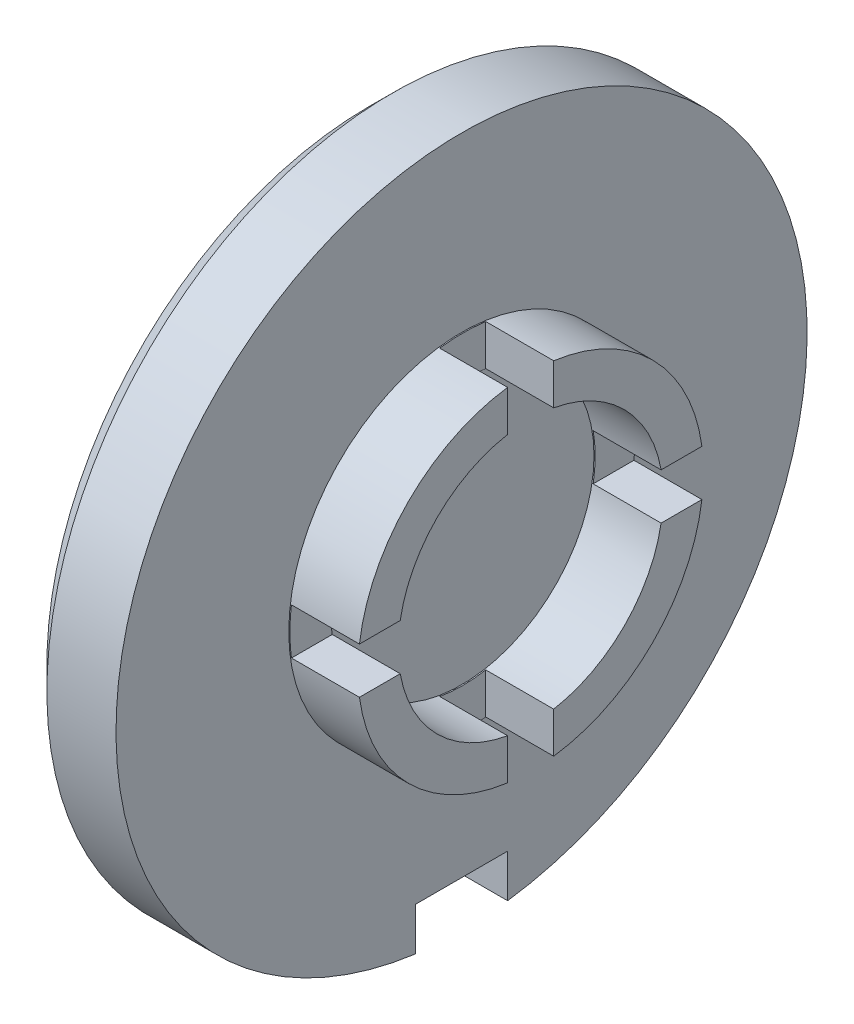
SolidWorks part; units mm, degrees
ref_plane "Front Plane" through (0, 0, 0) normal (0, 0, 1) x (1, 0, 0)
ref_plane "Top Plane" through (0, 0, 0) normal (0, 1, 0) x (1, 0, 0)
ref_plane "Right Plane" through (0, 0, 0) normal (1, 0, 0) x (0, 0, -1)
ref_plane "Plane1" through (0, 0, 66) normal (0, 0, 1) x (1, 0, 0)
sketch "Sketch1" plane through (0, 0, 66) normal (0, 0, 1) x (1, 0, 0)
  line L0 (-66, 18) -> (-53.2, 18) construction
  line L1 (-58.2, 20.3) -> (-59.4, 20.3)
  line L2 (-59.4, 20.3) -> (-59.4, 18)
  line L3 (-59.4, 18) -> (-61, 18)
  line L4 (-61, 18) -> (-61, 23.6)
  line L5 (-61, 23.6) -> (-60.6, 24)
  line L6 (-60.6, 24) -> (-59.4, 24)
  line L7 (-59.4, 24) -> (-59.4, 21)
  line L8 (-59.4, 21) -> (-58.2, 21)
  line L9 (-58.2, 21) -> (-58.2, 20.3)
revolve "Revolve1" add sketch "Sketch1" angle 360 about L0
sketch "Sketch2" plane through (0, 0, 0) normal (0, 0, 1) x (1, 0, 0)
  line L1 (-59.38, 17.6) -> (-58.1, 17.6)
  line L2 (-59.38, 17.6) -> (-59.38, 18.4)
  line L3 (-59.38, 18.4) -> (-58.1, 18.4)
  line L4 (-58.1, 17.6) -> (-58.1, 18.4)
extrude "Boss-Extrude1" add sketch "Sketch2" along normal blind 6.4 from offset 62.8 separate body
combine bodies "Combine1" operation type subtract main body 101 bodies to subtract 102
sketch "Sketch3" plane through (0, 0, 0) normal (0, 0, 1) x (1, 0, 0)
  line L1 (-59.38, 14.8) -> (-58.1, 14.8)
  line L2 (-59.38, 14.8) -> (-59.38, 21.2)
  line L3 (-59.38, 21.2) -> (-58.1, 21.2)
  line L4 (-58.1, 14.8) -> (-58.1, 21.2)
extrude "Boss-Extrude2" add sketch "Sketch3" along normal blind 0.8 from offset 65.6 separate body
combine bodies "Combine2" operation type subtract main body 103 bodies to subtract 104
sketch "Sketch4" plane through (0, 0, 0) normal (0, 0, 1) x (1, 0, 0)
  line L1 (-61.1, 11.9) -> (-59.3, 11.9)
  line L2 (-61.1, 11.9) -> (-61.1, 12.8)
  line L3 (-61.1, 12.8) -> (-59.3, 12.8)
  line L4 (-59.3, 11.9) -> (-59.3, 12.8)
extrude "Boss-Extrude3" add sketch "Sketch4" along normal blind 1.6 from offset 65.2 separate body
combine bodies "Combine3" operation type subtract main body 105 bodies to subtract 106
